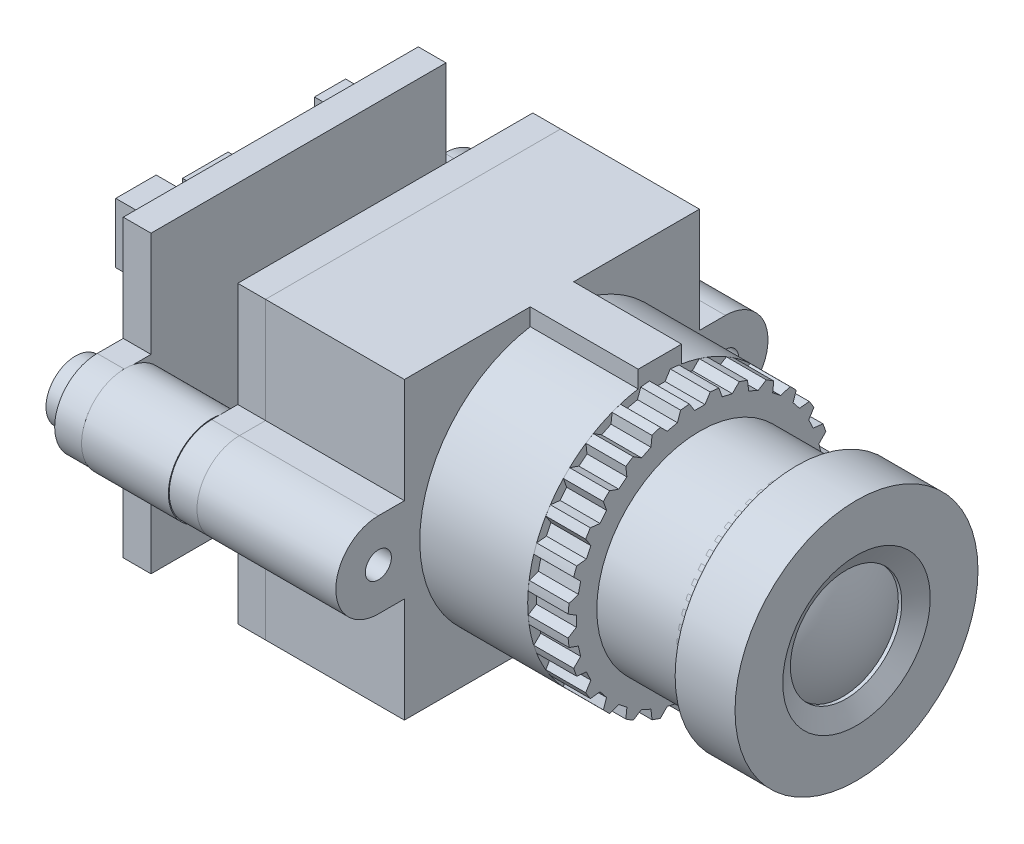
SolidWorks part; units mm, degrees
ref_plane "Front Plane" through (0, 0, 0) normal (0, 0, 1) x (1, 0, 0)
ref_plane "Top Plane" through (0, 0, 0) normal (0, 1, 0) x (1, 0, 0)
ref_plane "Right Plane" through (0, 0, 0) normal (1, 0, 0) x (0, 0, -1)
ref_axis "Axis1" through (-11.8965, 0, 0) along (1, 0, 0)
sketch "Sketch1" plane through (0, 0, 0) normal (1, 0, 0) x (0, 0, -1)
  circle A0 centre (0, 0) radius 7
  dimension "D1" = 14
extrude "Boss-Extrude1" add sketch "Sketch1" against normal blind 3.45
sketch "Sketch2" plane through (-3.45, 0, 0) normal (-1, 0, 0) x (0, 0, 1)
  circle A0 centre (0, 0) radius 5.935
  dimension "D1" = 11.87
extrude "Boss-Extrude2" add sketch "Sketch2" along normal blind 5.58
sketch "Sketch3" plane through (-9.03, 0, 0) normal (-1, 0, 0) x (0, 0, 1)
  circle A0 centre (0, 0) radius 7.61
  dimension "D1" = 15.22
extrude "Boss-Extrude3" add sketch "Sketch3" along normal blind 2.3
sketch "Sketch4" plane through (0, 0, 0) normal (0, 0, 1) x (1, 0, 0)
  line L0 (-3.45, 0) -> (0, 0) construction
  line L1 (-3.45, 5.935) -> (-3.45, -5.935) construction
  line L2 (0, -7) -> (0, 7) construction
  line L3 (0, 7) -> (-3.45, 7) construction
  line L4 (-0.6, 4.25) -> (0, 4.25)
  line L5 (-0.6, 4.25) -> (-0.6, -4.25)
  line L6 (-0.6, -4.25) -> (0, -4.25)
  line L7 (0, 4.25) -> (0, -4.25)
  line L8 (-0.6, 4.25) -> (0, -4.25) construction
  line L9 (-0.6, -4.25) -> (0, 4.25) construction
  line L10 (0, 4.25) -> (-0.6, 3.2108)
  line L11 (-0.8, 0) -> (-0.6, 3.2108) construction
  line L12 (-0.8, -3.2108) -> (-0.6, -3.2108)
  line L13 (-0.8, -3.2108) -> (-0.8, 3.2108)
  line L14 (-0.8, 3.2108) -> (-0.6, 3.2108)
  line L15 (-0.6, -3.2108) -> (-0.6, 3.2108)
  line L16 (-0.8, -3.2108) -> (-0.6, 3.2108) construction
  line L17 (-0.8, 3.2108) -> (-0.6, -3.2108) construction
  line L18 (-0.7, 1.6054) -> (0, 1.6054) construction
  line L19 (-0.8, 0) -> (0, 0)
  line L21 (0, 0) -> (0.6, 0)
  line L22 (0, 0) -> (0, 4.25)
  line L23 (0, 4.25) -> (0.6, 4.25)
  line L24 (0.6, 0) -> (0.6, 4.25)
  spline S0 degree 2 poles (0, 0) (0, 1.7034) (-0.8, 3.2108) knots 0 0 0 1 1 1
  point P6 (-0.3, 0)
  point P15 (-0.7, 0)
  dimension "D1" = 0.6
  dimension "D2" = 2.75
  dimension "D3" = 60
  dimension "D4" = 0.2
  dimension "D5" = 0.6
revolve "Cut-Revolve7" cut sketch "Sketch4" angle 360 about axis through (-11.8965, 0, 0) along (1, 0, 0) region at (0.3, 2.125, 0) region at (-0.2115, 2.72, 0) region at (-0.6658, 3.0768, 0)
sketch "Sketch5" plane through (-9.03, 0, 0) normal (1, 0, 0) x (0, 0, -1)
  line L0 (0, 7.61) -> (0, -7.61) construction
  line L1 (0.6, 7.5863) -> (0.3, 7.11)
  line L2 (0.3, 7.11) -> (-0.3, 7.11)
  line L3 (-0.6, 7.5863) -> (-0.3, 7.11)
  line L4 (2.2731, 7.2626) -> (1.8746, 6.865)
  line L5 (1.8746, 6.865) -> (1.2896, 6.9985)
  line L6 (1.1032, 7.5296) -> (1.2896, 6.9985)
  line L7 (3.8322, 6.5747) -> (3.3552, 6.2757)
  line L8 (3.3552, 6.2757) -> (2.8146, 6.5361)
  line L9 (2.751, 7.0954) -> (2.8146, 6.5361)
  line L10 (5.1991, 5.5571) -> (4.6676, 5.3718)
  line L11 (4.6676, 5.3718) -> (4.1985, 5.7459)
  line L12 (4.2609, 6.3053) -> (4.1985, 5.7459)
  line L13 (6.3053, 4.2609) -> (5.7459, 4.1985)
  line L14 (5.7459, 4.1985) -> (5.3718, 4.6676)
  line L15 (5.5571, 5.1991) -> (5.3718, 4.6676)
  line L16 (7.0954, 2.751) -> (6.5361, 2.8146)
  line L17 (6.5361, 2.8146) -> (6.2757, 3.3552)
  line L18 (6.5747, 3.8322) -> (6.2757, 3.3552)
  line L19 (7.5296, 1.1032) -> (6.9985, 1.2896)
  line L20 (6.9985, 1.2896) -> (6.865, 1.8746)
  line L21 (7.2626, 2.2731) -> (6.865, 1.8746)
  line L22 (7.5863, -0.6) -> (7.11, -0.3)
  line L23 (7.11, -0.3) -> (7.11, 0.3)
  line L24 (7.5863, 0.6) -> (7.11, 0.3)
  line L25 (7.2626, -2.2731) -> (6.865, -1.8746)
  line L26 (6.865, -1.8746) -> (6.9985, -1.2896)
  line L27 (7.5296, -1.1032) -> (6.9985, -1.2896)
  line L28 (6.5747, -3.8322) -> (6.2757, -3.3552)
  line L29 (6.2757, -3.3552) -> (6.5361, -2.8146)
  line L30 (7.0954, -2.751) -> (6.5361, -2.8146)
  line L31 (5.5571, -5.1991) -> (5.3718, -4.6676)
  line L32 (5.3718, -4.6676) -> (5.7459, -4.1985)
  line L33 (6.3053, -4.2609) -> (5.7459, -4.1985)
  line L34 (4.2609, -6.3053) -> (4.1985, -5.7459)
  line L35 (4.1985, -5.7459) -> (4.6676, -5.3718)
  line L36 (5.1991, -5.5571) -> (4.6676, -5.3718)
  line L37 (2.751, -7.0954) -> (2.8146, -6.5361)
  line L38 (2.8146, -6.5361) -> (3.3552, -6.2757)
  line L39 (3.8322, -6.5747) -> (3.3552, -6.2757)
  line L40 (1.1032, -7.5296) -> (1.2896, -6.9985)
  line L41 (1.2896, -6.9985) -> (1.8746, -6.865)
  line L42 (2.2731, -7.2626) -> (1.8746, -6.865)
  line L43 (-0.6, -7.5863) -> (-0.3, -7.11)
  line L44 (-0.3, -7.11) -> (0.3, -7.11)
  line L45 (0.6, -7.5863) -> (0.3, -7.11)
  line L46 (-2.2731, -7.2626) -> (-1.8746, -6.865)
  line L47 (-1.8746, -6.865) -> (-1.2896, -6.9985)
  line L48 (-1.1032, -7.5296) -> (-1.2896, -6.9985)
  line L49 (-3.8322, -6.5747) -> (-3.3552, -6.2757)
  line L50 (-3.3552, -6.2757) -> (-2.8146, -6.5361)
  line L51 (-2.751, -7.0954) -> (-2.8146, -6.5361)
  line L52 (-5.1991, -5.5571) -> (-4.6676, -5.3718)
  line L53 (-4.6676, -5.3718) -> (-4.1985, -5.7459)
  line L54 (-4.2609, -6.3053) -> (-4.1985, -5.7459)
  line L55 (-6.3053, -4.2609) -> (-5.7459, -4.1985)
  line L56 (-5.7459, -4.1985) -> (-5.3718, -4.6676)
  line L57 (-5.5571, -5.1991) -> (-5.3718, -4.6676)
  line L58 (-7.0954, -2.751) -> (-6.5361, -2.8146)
  line L59 (-6.5361, -2.8146) -> (-6.2757, -3.3552)
  line L60 (-6.5747, -3.8322) -> (-6.2757, -3.3552)
  line L61 (-7.5296, -1.1032) -> (-6.9985, -1.2896)
  line L62 (-6.9985, -1.2896) -> (-6.865, -1.8746)
  line L63 (-7.2626, -2.2731) -> (-6.865, -1.8746)
  line L64 (-7.5863, 0.6) -> (-7.11, 0.3)
  line L65 (-7.11, 0.3) -> (-7.11, -0.3)
  line L66 (-7.5863, -0.6) -> (-7.11, -0.3)
  line L67 (-7.2626, 2.2731) -> (-6.865, 1.8746)
  line L68 (-6.865, 1.8746) -> (-6.9985, 1.2896)
  line L69 (-7.5296, 1.1032) -> (-6.9985, 1.2896)
  line L70 (-6.5747, 3.8322) -> (-6.2757, 3.3552)
  line L71 (-6.2757, 3.3552) -> (-6.5361, 2.8146)
  line L72 (-7.0954, 2.751) -> (-6.5361, 2.8146)
  line L73 (-5.5571, 5.1991) -> (-5.3718, 4.6676)
  line L74 (-5.3718, 4.6676) -> (-5.7459, 4.1985)
  line L75 (-6.3053, 4.2609) -> (-5.7459, 4.1985)
  line L76 (-4.2609, 6.3053) -> (-4.1985, 5.7459)
  line L77 (-4.1985, 5.7459) -> (-4.6676, 5.3718)
  line L78 (-5.1991, 5.5571) -> (-4.6676, 5.3718)
  line L79 (-2.751, 7.0954) -> (-2.8146, 6.5361)
  line L80 (-2.8146, 6.5361) -> (-3.3552, 6.2757)
  line L81 (-3.8322, 6.5747) -> (-3.3552, 6.2757)
  line L82 (-1.1032, 7.5296) -> (-1.2896, 6.9985)
  line L83 (-1.2896, 6.9985) -> (-1.8746, 6.865)
  line L84 (-2.2731, 7.2626) -> (-1.8746, 6.865)
  circle A0 centre (0, 0) radius 7.61 construction
  circle A1 centre (0, 0) radius 7.61 construction
  circle A2 centre (0, 0) radius 7.61
  point P12 (0, 7.11)
  point P123 (0, 0)
  circle M6 centre (0, 0) radius 7.61
  dimension "D1" = 0.6
  dimension "D2" = 1.2
  dimension "D3" = 0.5
  dimension "D5" = 0.5063
  dimension "D4" = 28
extrude "Cut-Extrude1" cut sketch "Sketch5" against normal up to next (2.3 mm away) contours L9 L8 L7 M6 | L6 L5 L4 M6 | L0 L2 L1 M6 | L84 L83 L82 M6 | L0 A2 L3 L2 | L81 L80 L79 M6 | L78 L77 L76 M6 | L75 L74 L73 M6 | L72 L71 L70 M6 | L69 L68 L67 M6 | L66 L65 L64 M6 | L63 L62 L61 M6 | L60 L59 L58 M6 | L57 L56 L55 M6 | L51 L50 L49 M6 | L54 L53 L52 M6 | L48 L47 L46 M6 | L0 L44 L43 M6 | L44 L0 A2 L45 | L42 L41 L40 M6 | L39 L38 L37 M6 | L36 L35 L34 M6 | L33 L32 L31 M6 | L30 L29 L28 M6 | L27 L26 L25 M6 | L24 L23 L22 M6 | L21 L20 L19 M6 | L18 L17 L16 M6 | L15 L14 L13 M6 | L12 L11 L10 M6 region at (-9.03, 7.384, -0.233) region at (-9.03, 7.384, 0.233) region at (-9.03, -7.384, -0.233) region at (-9.03, -7.384, 0.233) region at (-9.03, 7.1989, -1.6431) region at (-9.03, 7.1989, 1.6431) region at (-9.03, 6.6527, -3.2038) region at (-9.03, 6.6527, 3.2038) region at (-9.03, -7.1989, 1.6431) region at (-9.03, -7.1989, -1.6431) region at (-9.03, 5.773, -4.6038) region at (-9.03, 5.773, 4.6038) region at (-9.03, -6.6527, 3.2038) region at (-9.03, -6.6527, -3.2038) region at (-9.03, 4.6038, -5.773) region at (-9.03, 4.6038, 5.773) region at (-9.03, -5.773, 4.6038) region at (-9.03, -5.773, -4.6038) region at (-9.03, 3.2038, -6.6527) region at (-9.03, 3.2038, 6.6527) region at (-9.03, -4.6038, 5.773) region at (-9.03, -4.6038, -5.773) region at (-9.03, 1.6431, -7.1989) region at (-9.03, 1.6431, 7.1989) region at (-9.03, -3.2038, 6.6527) region at (-9.03, -3.2038, -6.6527) region at (-9.03, 0, -7.384) region at (-9.03, 0, 7.384) region at (-9.03, -1.6431, 7.1989) region at (-9.03, -1.6431, -7.1989)
sketch "Sketch6" plane through (-11.33, 0, 0) normal (-1, 0, 0) x (0, 0, 1)
  line L0 (0, 7.615) -> (0, -7.615) construction
  line L2 (-8.5, -8.5) -> (8.5, -8.5)
  line L3 (-8.5, -8.5) -> (-8.5, 8.5)
  line L4 (-8.5, 8.5) -> (8.5, 8.5)
  line L5 (8.5, -8.5) -> (8.5, 8.5)
  line L6 (-8.5, -8.5) -> (8.5, 8.5) construction
  line L7 (-8.5, 8.5) -> (8.5, -8.5) construction
  line L8 (-1.25, 7.5117) -> (1.25, 7.5117)
  line L9 (-1.25, 7.5117) -> (-1.25, 8.5)
  line L10 (-1.25, 8.5) -> (1.25, 8.5)
  line L11 (1.25, 7.5117) -> (1.25, 8.5)
  line L12 (-1.25, 7.5117) -> (1.25, 8.5) construction
  line L13 (-1.25, 8.5) -> (1.25, 7.5117) construction
  circle A0 centre (0, 0) radius 7.615
  point P9 (0, 8.0059)
  dimension "D1" = 15.23
  dimension "D2" = 17
  dimension "D3" = 2.5
extrude "Boss-Extrude4" add sketch "Sketch6" along normal offset from surface (6.22 mm away) 17.55 contours L8 A0 | L8 A0 | A0 L11 L4 L9 region at (-11.33, 8.0398, 0) region at (-11.33, 7.553, 0) region at (-11.33, -0.0072, 0) up to face at (0, 0, 4.25)
sketch "Sketch7" plane through (-17.55, 0, 0) normal (-1, 0, 0) x (0, 0, 1)
  line L1 (-8.5, -8.5) -> (8.5, -8.5)
  line L2 (-8.5, -8.5) -> (-8.5, 8.5)
  line L3 (-8.5, 8.5) -> (8.5, 8.5)
  line L4 (8.5, -8.5) -> (8.5, 8.5)
  line L5 (-8.5, -8.5) -> (8.5, 8.5) construction
  line L6 (-8.5, 8.5) -> (8.5, -8.5) construction
  line L7 (-8.5, 0) -> (8.5, 0) construction
  line L8 (0, 8.5) -> (0, -8.5) construction
  line L9 (-10, 2.45) -> (-8.5, 2.45)
  line L10 (-10, -2.45) -> (-8.5, -2.45)
  line L11 (10, 2.45) -> (8.5, 2.45)
  line L12 (10, -2.45) -> (8.5, -2.45)
  circle A0 centre (-10, 0) radius 2.45
  circle A1 centre (-10, 0) radius 0.75
  circle A2 centre (10, 0) radius 0.75
  circle A3 centre (10, 0) radius 2.45
  point P0 (0, 0)
  dimension "D1" = 4.9
  dimension "D3" = 1.5
  dimension "D2" = 20
  dimension "D4" = 17
extrude "Boss-Extrude5" add sketch "Sketch7" along normal blind 8 contours A0 L10 L2 | L2 A0 A1 | A0 L2 L9 | L12 A3 L4 | A3 L4 A2 | L4 A3 L11 | L1 L4 L3 L2 region at (-17.55, -2.2994, -8.8667) region at (-17.55, -2.2994, 8.8667) region at (-17.55, -2.2587, -9.2277) region at (-17.55, 0, 8.5629) region at (-17.55, 2.2994, -8.8667) region at (-17.55, 2.2994, 8.8667)
sketch "Sketch8" plane through (-25.55, 0, 0) normal (-1, 0, 0) x (0, 0, 1)
  line L10 (-10, -2.45) -> (-8.5, -2.45)
  line L11 (-8.5, -2.45) -> (-8.5, -8.5)
  line L12 (-8.5, -8.5) -> (8.5, -8.5)
  line L13 (8.5, -8.5) -> (8.5, -2.45)
  line L14 (8.5, -2.45) -> (10, -2.45)
  line L15 (10, 2.45) -> (8.5, 2.45)
  line L16 (8.5, 2.45) -> (8.5, 8.5)
  line L17 (8.5, 8.5) -> (-8.5, 8.5)
  line L18 (-8.5, 8.5) -> (-8.5, 2.45)
  line L19 (-8.5, 2.45) -> (-10, 2.45)
  line L20 (-10, -2.45) -> (-8.5, -2.45)
  line L21 (-8.5, -2.45) -> (-8.5, -8.5)
  line L22 (-8.5, -8.5) -> (8.5, -8.5)
  line L23 (8.5, -8.5) -> (8.5, -2.45)
  line L24 (8.5, -2.45) -> (10, -2.45)
  line L25 (10, 2.45) -> (8.5, 2.45)
  line L26 (8.5, 2.45) -> (8.5, 8.5)
  line L27 (8.5, 8.5) -> (-8.5, 8.5)
  line L28 (-8.5, 8.5) -> (-8.5, 2.45)
  line L29 (-8.5, 2.45) -> (-10, 2.45)
  circle A0 centre (10, 0) radius 0.75 construction
  circle A1 centre (-10, 0) radius 0.75 construction
  arc A2 (10, -2.45) -> (10, 2.45) centre (10, 0) ccw
  arc A3 (-10, 2.45) -> (-10, -2.45) centre (-10, 0) ccw
  arc A4 (10, -2.45) -> (10, 2.45) centre (10, 0) ccw
  arc A5 (-10, 2.45) -> (-10, -2.45) centre (-10, 0) ccw
  circle A6 centre (10, 0) radius 0.75
  circle A7 centre (-10, 0) radius 0.75
  dimension "D1" = 0
extrude "Boss-Extrude6" add sketch "Sketch8" along normal blind 1.6 separate body
sketch "Sketch9" plane through (-27.15, 0, 0) normal (-1, 0, 0) x (0, 0, 1)
  line L0 (0, 8.5) -> (0, -8.5) construction
  line L1 (8.5, 8.5) -> (-8.5, 8.5) construction
  line L2 (-8.5, -8.5) -> (8.5, -8.5) construction
  circle A0 centre (-10, 0) radius 2.5
  circle A1 centre (-10, 0) radius 1
  circle A2 centre (10, 0) radius 2.5
  circle A3 centre (10, 0) radius 1
  dimension "D1" = 5
  dimension "D2" = 2
extrude "Boss-Extrude7" add sketch "Sketch9" along normal blind 5 separate body
sketch "Sketch10" plane through (-32.15, 0, 0) normal (-1, 0, 0) x (0, 0, 1)
  line L10 (-10, -2.45) -> (-8.5, -2.45)
  line L11 (-8.5, -2.45) -> (-8.5, -8.5)
  line L12 (-8.5, -8.5) -> (8.5, -8.5)
  line L13 (8.5, -8.5) -> (8.5, -2.45)
  line L14 (8.5, -2.45) -> (10, -2.45)
  line L15 (10, 2.45) -> (8.5, 2.45)
  line L16 (8.5, 2.45) -> (8.5, 8.5)
  line L17 (8.5, 8.5) -> (-8.5, 8.5)
  line L18 (-8.5, 8.5) -> (-8.5, 2.45)
  line L19 (-8.5, 2.45) -> (-10, 2.45)
  line L20 (-10, -2.45) -> (-8.5, -2.45)
  line L21 (-8.5, -2.45) -> (-8.5, -8.5)
  line L22 (-8.5, -8.5) -> (8.5, -8.5)
  line L23 (8.5, -8.5) -> (8.5, -2.45)
  line L24 (8.5, -2.45) -> (10, -2.45)
  line L25 (10, 2.45) -> (8.5, 2.45)
  line L26 (8.5, 2.45) -> (8.5, 8.5)
  line L27 (8.5, 8.5) -> (-8.5, 8.5)
  line L28 (-8.5, 8.5) -> (-8.5, 2.45)
  line L29 (-8.5, 2.45) -> (-10, 2.45)
  circle A0 centre (-10, 0) radius 0.75 construction
  circle A1 centre (10, 0) radius 0.75 construction
  arc A2 (-10, 2.45) -> (-10, -2.45) centre (-10, 0) ccw
  arc A3 (10, -2.45) -> (10, 2.45) centre (10, 0) ccw
  arc A4 (-10, 2.45) -> (-10, -2.45) centre (-10, 0) ccw
  arc A5 (10, -2.45) -> (10, 2.45) centre (10, 0) ccw
  circle A6 centre (10, 0) radius 0.75
  circle A7 centre (-10, 0) radius 0.75
  dimension "D1" = 0
extrude "Boss-Extrude8" add sketch "Sketch10" along normal blind 1.6 separate body
sketch "Sketch11" plane through (-33.75, 0, 0) normal (-1, 0, 0) x (0, 0, 1)
  line L0 (0, 8.5) -> (0, -8.5) construction
  line L1 (8.5, 8.5) -> (-8.5, 8.5) construction
  line L2 (-8.5, -8.5) -> (8.5, -8.5) construction
  line L4 (-3.5, -4.7) -> (3.5, -4.7)
  line L5 (-3.5, -4.7) -> (-3.5, -7.9)
  line L6 (-3.5, -7.9) -> (3.5, -7.9)
  line L7 (3.5, -4.7) -> (3.5, -7.9)
  line L8 (-3.5, -4.7) -> (3.5, -7.9) construction
  line L9 (-3.5, -7.9) -> (3.5, -4.7) construction
  point P6 (0, -6.3)
  dimension "D1" = 7
  dimension "D2" = 3.2
  dimension "D3" = 0.6
extrude "Boss-Extrude9" add sketch "Sketch11" along normal blind 4.8 separate body
sketch "Sketch12" plane through (-38.55, 0, 0) normal (-1, 0, 0) x (0, 0, 1)
  line L0 (-3.5, -4.7) -> (3.5, -7.9) construction
  line L1 (3.5, -7.9) -> (3.5, -4.7) construction
  line L2 (-3.15, -7.55) -> (3.15, -7.55)
  line L3 (-3.15, -7.55) -> (-3.15, -5.05)
  line L4 (-3.15, -5.05) -> (3.15, -5.05)
  line L5 (3.15, -7.55) -> (3.15, -5.05)
  line L6 (-3.15, -7.55) -> (3.15, -5.05) construction
  line L7 (-3.15, -5.05) -> (3.15, -7.55) construction
  line L8 (3.15, -5.05) -> (3.5, -5.05) construction
  line L9 (3.15, -5.05) -> (3.15, -4.7) construction
  line L10 (3.5, -4.7) -> (-3.5, -4.7) construction
  point P4 (0, -6.3)
  dimension "D1" = 0.35
extrude "Cut-Extrude2" cut sketch "Sketch12" against normal offset from surface (4.4 mm away) 0.4 up to face at (-33.75, 0, 10.75)
sketch "Sketch13" plane through (-38.55, 0, 0) normal (-1, 0, 0) x (0, 0, 1)
  line L0 (0, -5.05) -> (0, -4.7) construction
  line L1 (3.15, -5.05) -> (-3.15, -5.05) construction
  line L2 (3.5, -4.7) -> (-3.5, -4.7) construction
  line L4 (-2.4, -5.05) -> (2.4, -5.05)
  line L5 (-2.4, -5.05) -> (-2.4, -4.7)
  line L6 (-2.4, -4.7) -> (2.4, -4.7)
  line L7 (2.4, -5.05) -> (2.4, -4.7)
  line L8 (-2.4, -5.05) -> (2.4, -4.7) construction
  line L9 (-2.4, -4.7) -> (2.4, -5.05) construction
  point P6 (0, -4.875)
  dimension "D1" = 4.8
extrude "Cut-Extrude3" cut sketch "Sketch13" against normal blind 1.5
sketch "Sketch14" plane through (-33.75, 0, 0) normal (-1, 0, 0) x (0, 0, 1)
  line L1 (6.733, 7.4544) -> (4.4023, 7.4544)
  line L2 (6.733, 7.4544) -> (6.733, 3.9954)
  line L3 (6.733, 3.9954) -> (4.4023, 3.9954)
  line L4 (4.4023, 7.4544) -> (4.4023, 3.9954)
  line L5 (3.6255, -8.0463) -> (5.9191, -8.0463)
  line L6 (3.6255, -8.0463) -> (3.6255, -4.1064)
  line L7 (3.6255, -4.1064) -> (5.9191, -4.1064)
  line L8 (5.9191, -8.0463) -> (5.9191, -4.1064)
  line L9 (-2.5526, -1.9607) -> (-0.9249, -1.9607)
  line L10 (-2.5526, -1.9607) -> (-2.5526, -3.8844)
  line L11 (-2.5526, -3.8844) -> (-0.9249, -3.8844)
  line L12 (-0.9249, -1.9607) -> (-0.9249, -3.8844)
  line L13 (-3.4035, 2.1827) -> (0.8694, 2.1827)
  line L14 (-3.4035, 2.1827) -> (-3.4035, 0.222)
  line L15 (-3.4035, 0.222) -> (0.8694, 0.222)
  line L16 (0.8694, 2.1827) -> (0.8694, 0.222)
  line L17 (-6.511, 6.7885) -> (-4.7168, 6.7885)
  line L18 (-6.511, 6.7885) -> (-6.511, 3.9954)
  line L19 (-6.511, 3.9954) -> (-4.7168, 3.9954)
  line L20 (-4.7168, 6.7885) -> (-4.7168, 3.9954)
  line L21 (0.259, 6.5295) -> (2.8856, 6.5295)
  line L22 (0.259, 6.5295) -> (0.259, 5.1977)
  line L23 (0.259, 5.1977) -> (2.8856, 5.1977)
  line L24 (2.8856, 6.5295) -> (2.8856, 5.1977)
extrude "Boss-Extrude10" add sketch "Sketch14" along normal blind 2.2
sketch "Sketch15" plane through (-33.75, 0, 0) normal (-1, 0, 0) x (0, 0, 1)
  circle A0 centre (-10, 0) radius 1.7
  circle A1 centre (10, 0) radius 1.7
  dimension "D1" = 3.4
extrude "Boss-Extrude11" add sketch "Sketch15" along normal blind 1.25
sketch "Sketch16" plane through (-3.45, 0, 0) normal (-1, 0, 0) x (0, 0, 1)
  circle A0 centre (0, 0) radius 5.935 construction
  circle A1 centre (0, 0) radius 5.935
extrude "Boss-Extrude12" add sketch "Sketch16" along normal blind 1 separate body
ref_axis "Axis2" through (-40.4775, 0, 0) along (1, 0, 0)
ref_plane "Plane1" through (10, 0, 0) normal (1, 0, 0) x (0, 0, -1)
ref_plane "Plane2" through (-3.45, 0, 0) normal (-1, 0, 0) x (0, 0, 1)
ref_point "Camera position"
ref_point "Camera target"
